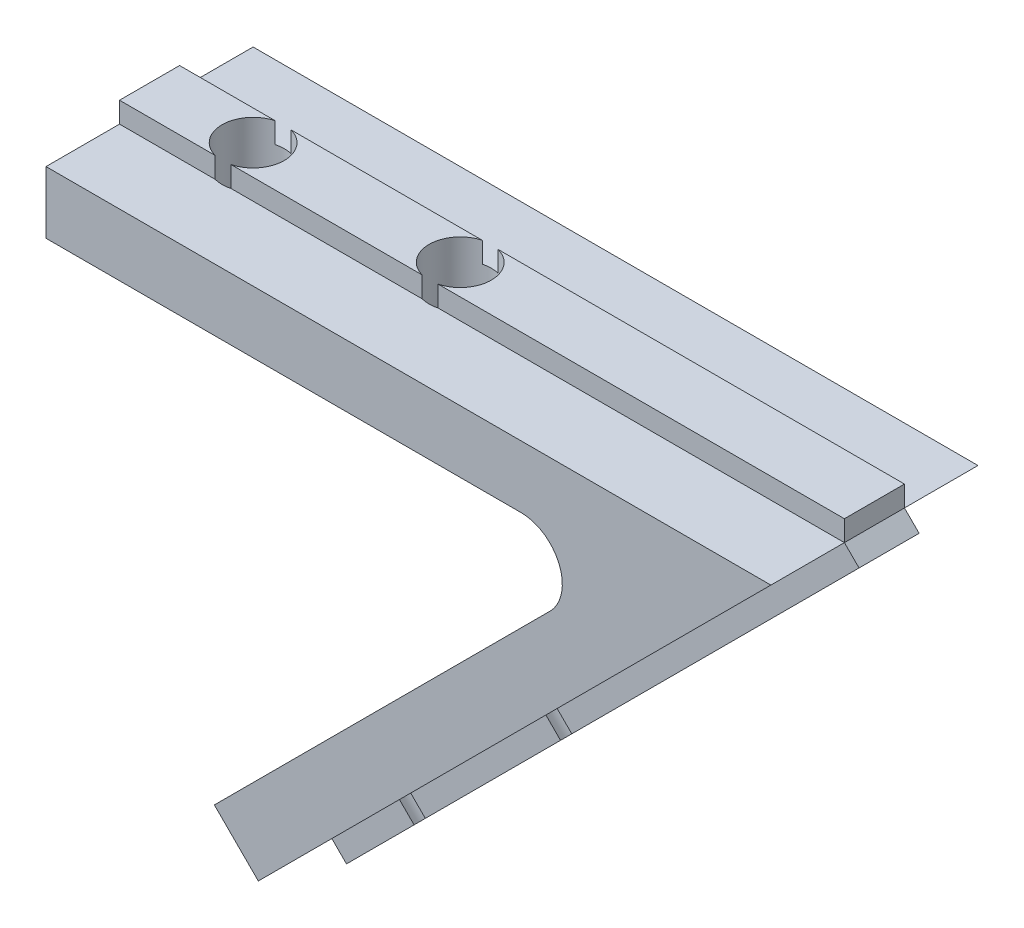
SolidWorks part; units mm, degrees
ref_plane "Front Plane" through (0, 0, 0) normal (0, 0, 1) x (1, 0, 0)
ref_plane "Top Plane" through (0, 0, 0) normal (0, 1, 0) x (1, 0, 0)
ref_plane "Right Plane" through (0, 0, 0) normal (1, 0, 0) x (0, 0, -1)
sketch "Esquisse1" plane through (0, 0, 0) normal (0, 0, 1) x (1, 0, 0)
  line L0 (0, 0) -> (35, 0)
  line L1 (35, 0) -> (10.2513, -24.7487)
  line L2 (10.2513, -24.7487) -> (8.1299, -22.6274)
  line L3 (8.1299, -22.6274) -> (24.3431, -6.4142)
  line L4 (0, 0) -> (0, -3)
  line L5 (0, -3) -> (22.9289, -3)
  arc A0 (24.3431, -6.4142) -> (22.9289, -3) centre (22.9289, -5) ccw
  point P6 (8.1134, -25.7324)
  point P8 (26.1918, -8.9091)
  point P9 (26.9202, -5.3885)
  dimension "D3" = 2
  dimension "D1" = 45
  dimension "D2" = 3
  dimension "D4" = 35
extrude "Boss.-Extru.1" add sketch "Esquisse1" along normal blind 10
sketch "Esquisse2" plane through (0, 0, 0) normal (0, 1, 0) x (1, 0, 0)
  line L0 (0, -10) -> (0, 0) construction
  line L1 (0, -6.45) -> (35, -6.45)
  line L2 (0, -6.45) -> (0, -3.55)
  line L3 (0, -3.55) -> (35, -3.55)
  line L4 (35, -6.45) -> (35, -3.55)
  line L5 (35, -10) -> (35, 0) construction
  point P8 (35, -5)
  point P9 (35, -5)
  dimension "D1" = 2.9
extrude "Boss.-Extru.2" add sketch "Esquisse2" along normal blind 1
sketch "Esquisse3" plane through (17.5, -17.5, 0) normal (0.7071, -0.7071, 0) x (0.7071, 0.7071, 0)
  line L1 (-10.2513, 3.55) -> (24.7487, 3.55)
  line L2 (-10.2513, 3.55) -> (-10.2513, 6.45)
  line L3 (-10.2513, 6.45) -> (24.7487, 6.45)
  line L4 (24.7487, 3.55) -> (24.7487, 6.45)
  line L5 (-10.2513, 10) -> (-10.2513, 0) construction
  line L6 (24.7487, 6.45) -> (24.7487, 3.55) construction
  point P4 (-10.2513, 5)
  point P5 (-10.2513, 5)
extrude "Boss.-Extru.3" add sketch "Esquisse3" along normal blind 1
sketch "Esquisse4" plane through (0, -3, 0) normal (0, -1, 0) x (1, 0, 0)
  line L0 (0, 10) -> (0, 0) construction
  circle A0 centre (5, 5) radius 1.5
  circle A1 centre (15, 5) radius 1.5
  point P4 (0, 0)
  point P5 (0, 0)
  point P8 (0, 5)
  point P9 (0, 0)
  dimension "D1" = 3
  dimension "D2" = 5
  dimension "D3" = 10
extrude "Enlèv. mat.-Extru.1" cut sketch "Esquisse4" against normal through all
sketch "Esquisse5" plane through (15.3787, -15.3787, 0) normal (-0.7071, 0.7071, 0) x (0.7071, 0.7071, 0)
  line L0 (-10.2513, -10) -> (-10.2513, 0) construction
  circle A0 centre (-5.2513, -5) radius 1.5
  circle A1 centre (4.7487, -5) radius 1.5
  point P6 (0, 0)
  point P7 (-10.2513, -5)
  dimension "D1" = 3
  dimension "D2" = 5
  dimension "D3" = 10
extrude "Enlèv. mat.-Extru.2" cut sketch "Esquisse5" against normal through all
